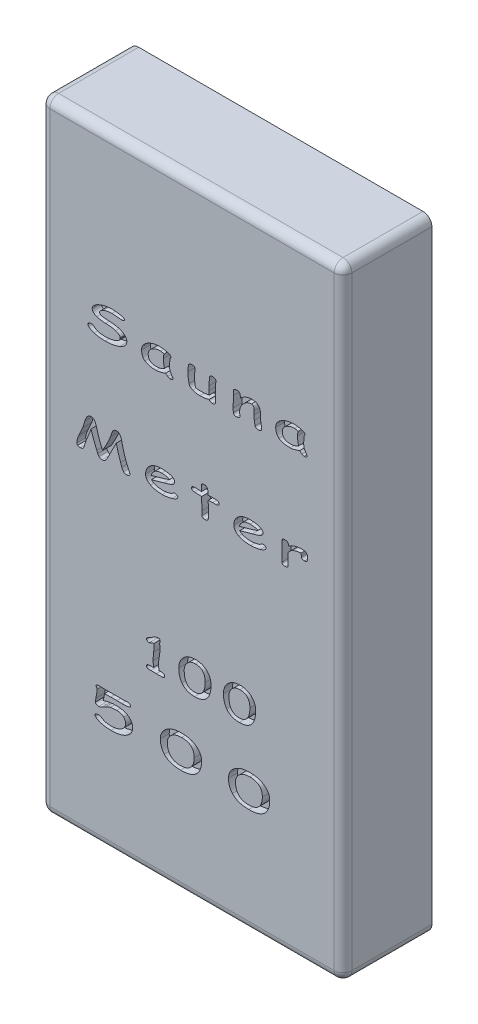
SolidWorks part; units mm, degrees
ref_plane "Front Plane" through (0, 0, 0) normal (0, 0, 1) x (1, 0, 0)
ref_plane "Top Plane" through (0, 0, 0) normal (0, 1, 0) x (1, 0, 0)
ref_plane "Right Plane" through (0, 0, 0) normal (1, 0, 0) x (0, 0, -1)
sketch "Sketch1" plane through (0, 0, 0) normal (0, 0, 1) x (1, 0, 0)
  line L5 (0, 0) -> (34, 0)
  line L6 (0, 0) -> (0, 70)
  line L7 (0, 70) -> (34, 70)
  line L8 (34, 0) -> (34, 70)
  dimension "D1" = 34
  dimension "D2" = 70
extrude "Boss-Extrude1" add sketch "Sketch1" along normal blind 10
sketch "Sketch2" plane through (0, 0, 0) normal (0, 0, -1) x (-1, 0, 0)
  line L0 (-34, 70) -> (0, 70) construction
  line L1 (-32, 68) -> (-2, 68)
  line L2 (-32, 68) -> (-32, 2)
  line L3 (-32, 2) -> (-2, 2)
  line L4 (-2, 68) -> (-2, 2)
  line L5 (0, 70) -> (0, 0) construction
  line L6 (-34, 0) -> (-34, 70) construction
  point P4 (-17, 68)
  point P7 (-17, 70)
  point P8 (-2, 35)
  point P11 (0, 35)
  dimension "D1" = 2
  dimension "D2" = 2
extrude "Cut-Extrude1" cut sketch "Sketch2" against normal blind 8
sketch "Sketch3" plane through (0, 0, 0) normal (0, 0, -1) x (-1, 0, 0)
  line L0 (-34, 70) -> (0, 70) construction
  line L1 (-34, 0) -> (-34, 70) construction
  line L2 (0, 70) -> (0, 0) construction
  line L3 (0, 0) -> (-34, 0) construction
  circle A0 centre (-31, 67) radius 3
  circle A1 centre (-3, 67) radius 3
  circle A2 centre (-3, 3) radius 3
  circle A3 centre (-31, 3) radius 3
  point P16 (0, 0)
  point P17 (0, 0)
  point P18 (0, 0)
  point P19 (0, 0)
  dimension "D1" = 6
  dimension "D2" = 6
  dimension "D3" = 6
  dimension "D4" = 6
extrude "Boss-Extrude2" add sketch "Sketch3" against normal up to surface (8 mm away) up to face at (17, 35, 8)
sketch "Sketch4" plane through (0, 0, 0) normal (0, 0, -1) x (-1, 0, 0)
  circle A0 centre (-3, 67) radius 1.5
  circle A1 centre (-31, 67) radius 1.5
  circle A2 centre (-3, 3) radius 1.5
  circle A3 centre (-31, 3) radius 1.5
  point P11 (-25.4815, 12.863)
  point P12 (0, 0)
  point P13 (0, 0)
  dimension "D1" = 3
  dimension "D2" = 3
  dimension "D3" = 3
  dimension "D4" = 3
extrude "Cut-Extrude2" cut sketch "Sketch4" against normal offset from surface (8 mm away) 2 up to face at (17, 35, 10)
sketch "Sketch5" plane through (0, 0, 10) normal (0, 0, 1) x (1, 0, 0)
  text T0 "Sauna" font "Comic Sans MS" height 3.5
  text T1 "Meter" font "Comic Sans MS" height 3.5
  text T2 "100" font "Comic Sans MS" height 3.5
  text T3 "500" font "Comic Sans MS" height 3.5
  point P1 (5.8556, 52.2515)
  point P2 (6.2123, 50.9142)
  point P4 (3.8155, 37.041)
  point P5 (0, 0)
  point P6 (4.6824, 49.6108)
  point P7 (0, 0)
  point P8 (0, 0)
  point P9 (0, 0)
  point P10 (4.6824, 41.4621)
  point P11 (2.3418, 40.1618)
  point P12 (5.9827, 50.5644)
extrude "Cut-Extrude3" cut sketch "Sketch5" against normal blind 1
sketch "Sketch6" plane through (0, 0, 0) normal (0, -1, 0) x (1, 0, 0)
  line L0 (9.5, 0) -> (24.5, 0) construction
  line L1 (0, 0) -> (34, 0) construction
  circle A0 centre (9.5, 0) radius 2
  circle A1 centre (24.5, 0) radius 2.5
  point P5 (17, 0)
  point P6 (17, 0)
  dimension "D1" = 4
  dimension "D2" = 5
  dimension "D3" = 15
extrude "Cut-Extrude4" cut sketch "Sketch6" against normal up to next
fillet "Fillet1" radius 1 4 edges at (34, 70, 5) (0, 70, 5) (0, 0, 5) (34, 0, 5)
fillet "Fillet2" radius 1 8 edges at (33.7071, 69.7071, 10) (34, 35, 10) (33.7071, 0.2929, 10) (17, 0, 10) (0.2929, 0.2929, 10) (0, 35, 10) (0.2929, 69.7071, 10) (17, 70, 10)
